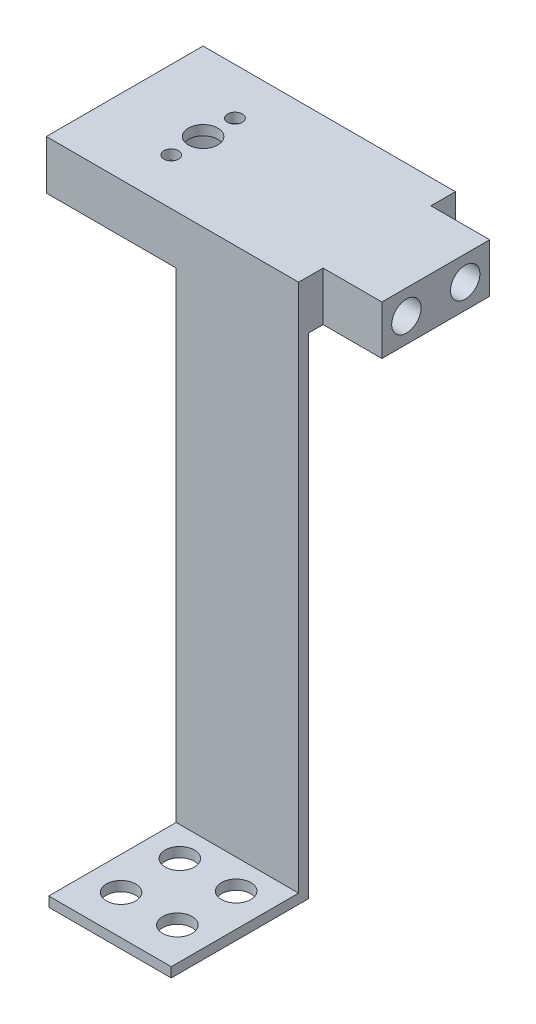
SolidWorks part; units mm, degrees
ref_plane "Front Plane" through (0, 0, 0) normal (0, 0, 1) x (1, 0, 0)
ref_plane "Top Plane" through (0, 0, 0) normal (0, 1, 0) x (1, 0, 0)
ref_plane "Right Plane" through (0, 0, 0) normal (1, 0, 0) x (0, 0, -1)
sketch "Sketch1" plane through (0, 0, 0) normal (0, 1, 0) x (1, 0, 0)
  line L0 (5.5, 11) -> (5.5, 16)
  line L1 (5.5, 11) -> (17.5, 11)
  line L3 (5.5, -11) -> (17.5, -11)
  line L4 (17.5, 11) -> (17.5, -11)
  line L5 (0, 0) -> (17.5, -11) construction
  line L6 (0, 0) -> (17.5, 11) construction
  line L7 (5.5, 16) -> (-46, 16)
  line L8 (-46, 16) -> (-46, -16)
  line L9 (-46, -16) -> (5.5, -16)
  line L10 (5.5, -16) -> (5.5, -11)
  point P0 (0, 0)
  dimension "D1" = 22
  dimension "D2" = 12
  dimension "D3" = 12
  dimension "D4" = 16
  dimension "D5" = 16
  dimension "D6" = 46
extrude "Boss-Extrude1" add sketch "Sketch1" along normal blind 10
sketch "Sketch2" plane through (17.5, 0, 0) normal (1, 0, 0) x (0, 0, -1)
  line L0 (-11, 0) -> (11, 0) construction
  line L1 (-11, 10) -> (-11, 0) construction
  line L2 (11, 10) -> (11, 0) construction
  circle A0 centre (-6, 5) radius 3
  circle A1 centre (6, 5) radius 3
  dimension "D1" = 5
  dimension "D2" = 5
  dimension "D3" = 5
  dimension "D4" = 5
extrude "Cut-Extrude1" cut sketch "Sketch2" against normal blind 10
sketch "Sketch4" plane through (0, 0, 0) normal (0, -1, 0) x (1, 0, 0)
  circle A0 centre (-30, 0) radius 11
  dimension "D1" = 30
extrude "Cut-Extrude3" cut sketch "Sketch4" against normal blind 8
sketch "Sketch5" plane through (0, 8, 0) normal (0, -1, 0) x (-1, 0, 0)
  circle A0 centre (30, 0) radius 3
  circle A3 centre (30, 6.5) radius 1.5
  circle A4 centre (30, -6.5) radius 1.5
  dimension "D1" = 6.5
  dimension "D2" = 6.5
extrude "Cut-Extrude4" cut sketch "Sketch5" against normal blind 8
sketch "Sketch7" plane through (0, 0, 0) normal (0, -1, 0) x (-1, 0, 0)
  line L1 (-5.5, -16) -> (19.5, -16)
  line L2 (-5.5, -16) -> (-5.5, -14)
  line L3 (-5.5, -14) -> (19.5, -14)
  line L4 (19.5, -16) -> (19.5, -14)
  dimension "D1" = 25
  dimension "D2" = 2
extrude "Boss-Extrude2" add sketch "Sketch7" along normal blind 100
sketch "Sketch8" plane through (0, 0, 14) normal (0, 0, -1) x (-1, 0, 0)
  line L0 (-5.5, -100) -> (-5.5, 0) construction
  line L1 (19.5, -100) -> (-5.5, -100)
  line L2 (19.5, -100) -> (19.5, -98)
  line L3 (19.5, -98) -> (-5.5, -98)
  line L4 (-5.5, -100) -> (-5.5, -98)
  dimension "D1" = 2
extrude "Boss-Extrude3" add sketch "Sketch8" against normal blind 28
sketch "Sketch9" plane through (0, -100, 0) normal (0, -1, 0) x (-1, 0, 0)
  line L1 (19.5, -14) -> (-5.5, -14) construction
  line L2 (-5.5, -42) -> (19.5, -42) construction
  line L7 (19.5, -42) -> (19.5, -14) construction
  circle A2 centre (1.25, -22) radius 3
  circle A3 centre (12.75, -22) radius 3
  circle A4 centre (1.25, -34) radius 3
  circle A5 centre (12.75, -34) radius 3
  dimension "D1" = 8
  dimension "D2" = 8
  dimension "D4" = 8
  dimension "D3" = 6.75
  dimension "D5" = 8
extrude "Cut-Extrude6" cut sketch "Sketch9" against normal blind 12
